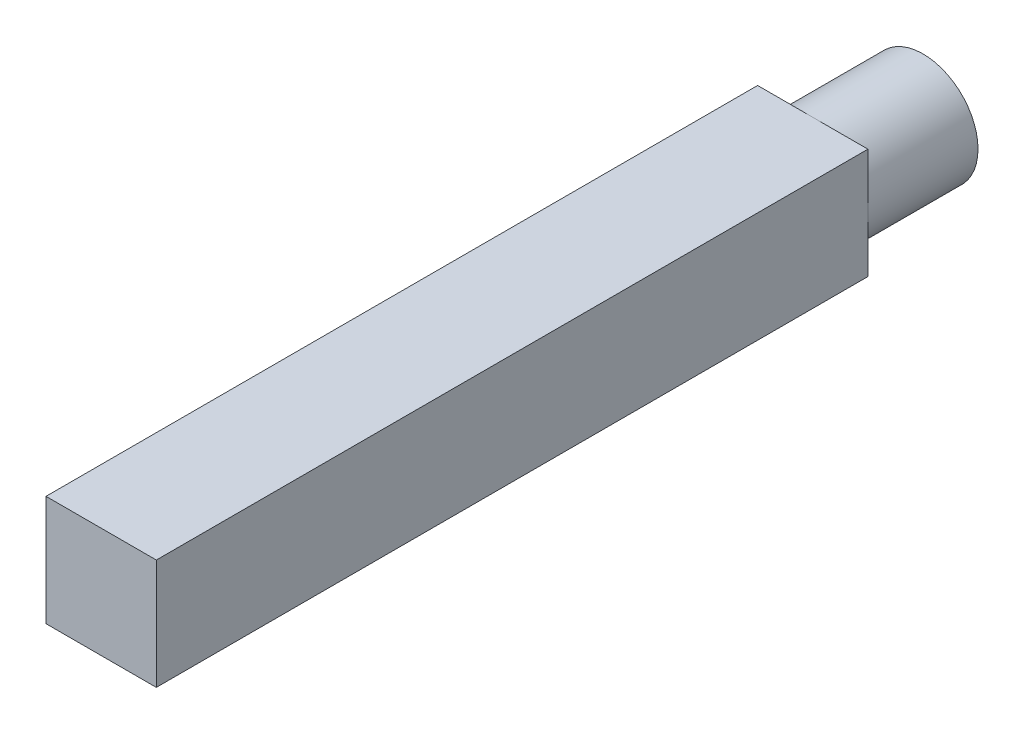
SolidWorks part; units mm, degrees
ref_plane "Front Plane" through (0, 0, 0) normal (0, 0, 1) x (1, 0, 0)
ref_plane "Top Plane" through (0, 0, 0) normal (0, 1, 0) x (1, 0, 0)
ref_plane "Right Plane" through (0, 0, 0) normal (1, 0, 0) x (0, 0, -1)
sketch "Sketch1" plane through (0, 0, 0) normal (0, 0, 1) x (1, 0, 0)
  line L1 (2, -2) -> (-2, -2)
  line L2 (2, -2) -> (2, 2)
  line L3 (2, 2) -> (-2, 2)
  line L4 (-2, -2) -> (-2, 2)
  line L5 (2, -2) -> (-2, 2) construction
  line L6 (2, 2) -> (-2, -2) construction
  dimension "D2" = 4
extrude "Boss-Extrude1" add sketch "Sketch1" along normal mid plane 27.8
sketch "Sketch2" plane through (0, 0, 13.9) normal (0, 0, 1) x (1, 0, 0)
  circle A0 centre (0, 0) radius 1.99
  dimension "D1" = 3.98
extrude "Boss-Extrude2" add sketch "Sketch2" along normal blind 4
mirror "Mirror2" about plane through (0, 0, 0) normal (0, 0, 1) of "Boss-Extrude2"
sketch "Sketch3" plane through (0, 2, 0) normal (0, 1, 0) x (1, 0, 0)
  line L2 (-2, -17.9) -> (-2, -11.9)
  line L3 (-2, -11.9) -> (2, -11.9)
  line L4 (2, -17.9) -> (2, -11.9)
  line L5 (2, -13.9) -> (2, 13.9) construction
  line L6 (-1.99, -17.9) -> (1.99, -17.9) construction
  line L7 (-2, -17.9) -> (2, -17.9)
  line L9 (-2, -13.9) -> (-2, 13.9) construction
  point P4 (0, 0)
  point P5 (-4.1294, -17.9)
  point P8 (5.46, -17.9)
  point P9 (7.0659, -17.9)
  point P10 (0, 0)
  point P14 (0, 0)
  dimension "D1" = 6
extrude "Cut-Extrude1" cut sketch "Sketch3" against normal up to next
